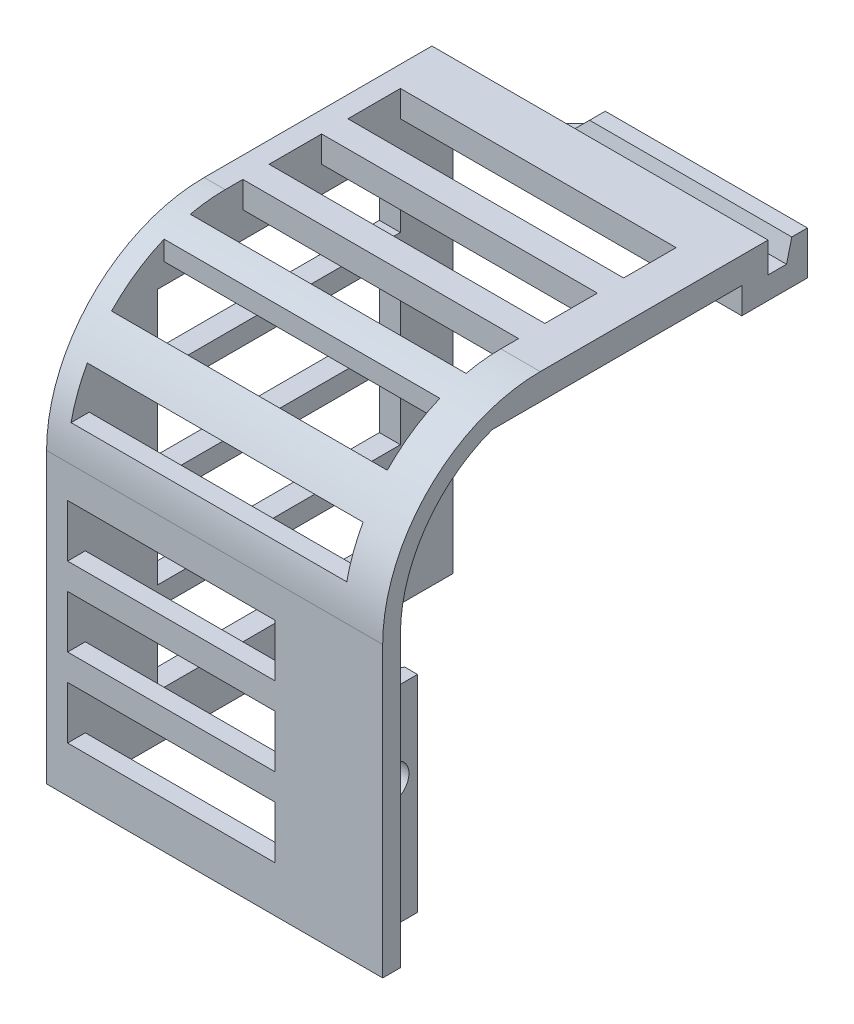
SolidWorks part; units mm, degrees
material "Nylon 6/10"
ref_plane "Front Plane" through (0, 0, 0) normal (0, 0, 1) x (1, 0, 0)
ref_plane "Top Plane" through (0, 0, 0) normal (0, 1, 0) x (1, 0, 0)
ref_plane "Right Plane" through (0, 0, 0) normal (1, 0, 0) x (0, 0, -1)
sketch "Sketch1" plane through (0, 0, 0) normal (1, 0, 0) x (0, 0, -1)
  line L0 (-2, 32) -> (-2, 30)
  line L2 (-2, 30) -> (0, 30)
  line L10 (1.408, 3) -> (0, 3) construction
  line L28 (-17.35, 34) -> (0, 34)
  line L29 (-28, 22) -> (-28, 15.7)
  line L30 (-23.7, 15.7) -> (-28, 15.7)
  line L31 (-28, 0) -> (-28, 15.7) construction
  line L33 (0, 34) -> (0, 32) construction
  line L34 (0, 34) -> (0, 30)
  line L37 (-2, 32) -> (-21.0137, 32)
  line L42 (-23.3, 15.7) -> (-16.7, 15.7) construction
  line L44 (1.408, 3) -> (0, 3) construction
  line L51 (-23.7, 15.7) -> (-23.7, 0)
  line L52 (-23.3, 3.3) -> (-23.3, 15.7) construction
  line L53 (-29.35, 0) -> (0, 0) construction
  line L54 (-28, 0) -> (0, 0) construction
  line L57 (-29.35, 0) -> (-23.7, 0)
  line L59 (-29.35, 22) -> (-29.35, 0) construction
  line L60 (-2.65, 15.701) -> (-20.95, 15.701) construction
  line L61 (-29.35, 22) -> (-29.35, 0)
  line L62 (-0.2, 3.8) -> (-0.2, 15.2) construction
  line L64 (-2.65, 15.701) -> (-20.95, 15.701) construction
  line L65 (-21.4252, 3.3) -> (-2.1748, 3.3) construction
  line L66 (-21.4252, 3.3) -> (-2.1748, 3.3) construction
  line L67 (-23.4, 15.2) -> (-23.4, 3.8) construction
  line L68 (-23.4, 15.2) -> (-23.4, 3.8) construction
  line L69 (-0.2, 3.8) -> (-0.2, 15.2) construction
  line L70 (4.4, 3.7) -> (4.4, 9.05) construction
  line L71 (4.4, 3.7) -> (4.4, 9.05) construction
  arc A0 (-21.0137, 32) -> (-28, 22) centre (-17.35, 22) ccw
  arc A2 (-17.35, 34) -> (-29.35, 22) centre (-17.35, 22) ccw construction
  circle A4 centre (-25.65, 9.5) radius 1.3 construction
  circle A5 centre (-25.65, 9.5) radius 1.3 construction
  arc A6 (3.1624, 9.95) -> (3.1624, 9.05) centre (2.05, 9.5) ccw construction
  arc A7 (3.1624, 9.95) -> (3.1624, 9.05) centre (2.05, 9.5) ccw construction
  arc A8 (-17.35, 34) -> (-29.35, 22) centre (-17.35, 22) ccw
  dimension "D1" = 2
  dimension "D2" = 2
  dimension "D3" = 1.35
  dimension "D4" = 0.4
  dimension "D5" = 2
extrude "Boss-Extrude1" add sketch "Sketch1" against normal offset from surface (25.6 mm away) 0.4
sketch "Sketch2" plane through (0, 0, 0) normal (1, 0, 0) x (0, 0, -1)
  line L0 (-23.7, 15.7) -> (-28, 15.7) construction
  line L1 (-23.7, 15.7) -> (-28, 15.7)
  line L2 (-23.7, 0) -> (-23.7, 15.7) construction
  line L3 (-23.7, 0) -> (-23.7, 15.7)
  line L6 (-28, 15.7) -> (-28, 0)
  line L7 (-23.7, 0) -> (-28, 0)
  line L8 (-29.35, 0) -> (-23.7, 0) construction
extrude "Cut-Extrude1" cut sketch "Sketch2" against normal blind 3
sketch "Sketch3" plane through (-3, 0, 0) normal (1, 0, 0) x (0, 0, -1)
  circle A0 centre (-25.65, 9.5) radius 1.3 construction
  circle A1 centre (-25.65, 9.5) radius 1.3
extrude "Cut-Extrude2" cut sketch "Sketch3" against normal up to next
sketch "Sketch4" plane through (-25.6, 0, 0) normal (-1, 0, 0) x (0, 0, 1)
  line L8 (0, 34) -> (0, 30)
  line L9 (0, 34) -> (0, 0)
  line L10 (17.35, 34) -> (0, 34)
  line L13 (0, 30) -> (2, 30)
  line L14 (2, 32) -> (21.0137, 32)
  line L15 (28, 22) -> (28, 15.7)
  line L16 (28, 15.7) -> (23.7, 15.7)
  line L17 (23.7, 15.7) -> (23.7, 0)
  line L18 (23.7, 0) -> (29.35, 0)
  line L19 (29.35, 0) -> (29.35, 22)
  line L20 (17.35, 34) -> (0, 34)
  line L28 (0, 0) -> (29.35, 0)
  line L29 (29.35, 0) -> (29.35, 22)
  line L31 (2, 30) -> (2, 32)
  arc A2 (29.35, 22) -> (17.35, 34) centre (17.35, 22) ccw
  arc A3 (28, 22) -> (21.0137, 32) centre (17.35, 22) ccw
  arc A4 (29.35, 22) -> (17.35, 34) centre (17.35, 22) ccw
  point P0 (4.8173, 0)
  dimension "D1" = 0
extrude "Boss-Extrude2" add sketch "Sketch4" against normal blind 1.6
sketch "Sketch6" plane through (0, 0, 0) normal (0, 0, -1) x (-1, 0, 0)
  line L0 (0, 32) -> (23, 32) construction
  line L1 (0, 32) -> (23, 32) construction
  line L2 (0, 31.7) -> (20, 31.7)
  line L3 (0, 30) -> (0, 34) construction
  line L4 (20, 31.7) -> (20, 30)
  line L5 (24, 30) -> (0, 30) construction
  line L6 (20, 30) -> (0, 30)
  line L7 (0, 30) -> (0, 31.7)
  point P6 (0, 0)
  dimension "D1" = 0.3
  dimension "D2" = 3
extrude "Boss-Extrude3" add sketch "Sketch6" along normal blind 3
chamfer "Chamfer2" distance 3 angle 45 1 edges at (-20, 30.85, -3)
sketch "Sketch8" plane through (0, 0, 0) normal (-1, 0, 0) x (0, 0, 1)
  line L0 (-1.408, 32) -> (-1.408, 34) construction
  line L1 (-1.408, 32) -> (-1.408, 34) construction
  line L2 (-1.408, 31.7) -> (-1.808, 33.3)
  line L3 (-3, 31.7) -> (0, 31.7) construction
  line L4 (-1.808, 33.3) -> (-3, 33.3)
  line L5 (-3, 33.3) -> (-3, 31.7)
  line L6 (-3, 31.7) -> (-1.408, 31.7)
  point P6 (-1.408, 31.7)
  point P8 (0, 0)
  point P9 (0, 0)
  point P10 (0, 0)
  point P11 (-1.5848, 32)
  point P12 (0, 0)
  point P14 (0, 0)
  point P15 (0, 0)
  dimension "D1" = 0.4
  dimension "D2" = 1.6
extrude "Boss-Extrude5" add sketch "Sketch8" along normal up to vertex (17 mm away) up to point (-17, 31.7, -3)
chamfer "Chamfer3" distance 1.6 angle 45 1 edges at (-17, 33.3, -2.404)
sketch "Sketch9" plane through (-24, 0, 0) normal (1, 0, 0) x (0, 0, -1)
  line L0 (-22.5137, 24.5) -> (-4, 24.5)
  line L1 (-4, 24.5) -> (-4, 30)
  line L2 (-4, 30) -> (-22.5137, 30)
  line L3 (-22.5137, 30) -> (-22.5137, 24.5)
  line L8 (-4, 30) -> (-4, 32) construction
  line L10 (0, 30) -> (0, 0) construction
  line L11 (-21.0137, 32) -> (-2, 32) construction
  dimension "D1" = 1.5
  dimension "D2" = 2
  dimension "D3" = 4
  dimension "D4" = 5.5
extrude "Cut-Extrude3" cut sketch "Sketch9" against normal up to next
pattern_linear "LPattern1" count 4 spacing 7 along (0, -1, 0) of "Cut-Extrude3"
sketch "Sketch10" plane through (0, 34, 0) normal (0, 1, 0) x (1, 0, 0)
  line L0 (-24, -8) -> (-3, -8)
  line L1 (-3, -8) -> (-3, -4)
  line L2 (-3, -4) -> (-24, -4)
  line L3 (-24, -4) -> (-24, -8)
  line L4 (-25.6, -4) -> (-24, -4) construction
  line L5 (-24, 0) -> (-24, -23.7) construction
  line L6 (0, -21.0137) -> (0, -2) construction
  dimension "D1" = 4
  dimension "D2" = 0
  dimension "D3" = 3
extrude "Cut-Extrude4" cut sketch "Sketch10" against normal up to next
pattern_linear "LPattern2" count 4 spacing 6 along (0, 0, 1) of "Cut-Extrude4"
sketch "Sketch11" plane through (-24, 0, 0) normal (1, 0, 0) x (0, 0, -1)
  line L4 (-23.7, 0) -> (-23.7, 15.7)
  line L5 (-23.7, 15.7) -> (-28, 15.7)
  line L6 (-28, 15.7) -> (-28, 0)
  line L7 (-28, 0) -> (-23.7, 0)
  line L8 (-23.7, 0) -> (-23.7, 15.7)
  line L9 (-23.7, 15.7) -> (-28, 15.7)
  line L11 (-28, 0) -> (-23.7, 0)
  line L12 (-28, 15.7) -> (-28, 0)
  dimension "D1" = 0
extrude "Cut-Extrude5" cut sketch "Sketch11" along normal offset from surface (20 mm away) 1 up to face at (-3, 9.5, 24.35)
chamfer "Chamfer4" distance 4.2 angle 45 1 edges at (-4, 7.85, 28)
sketch "Sketch12" plane through (0, 0, 28) normal (0, 0, -1) x (-1, 0, 0)
  line L0 (8.2, 3.5) -> (24, 3.5)
  line L1 (8.2, 15.7) -> (8.2, 0) construction
  line L2 (24, 0) -> (24, 22) construction
  line L3 (24, 3.5) -> (24, 7.5)
  line L4 (24, 7.5) -> (8.2, 7.5)
  line L5 (8.2, 7.5) -> (8.2, 3.5)
  line L7 (25.6, 3.5) -> (24, 3.5) construction
  dimension "D1" = 4
extrude "Cut-Extrude6" cut sketch "Sketch12" against normal up to next
pattern_linear "LPattern3" count 3 spacing 6 along (0, 1, 0) of "Cut-Extrude6"
sketch "Sketch13" plane through (0, 0, 29.35) normal (0, 0, 1) x (1, 0, 0)
  line L0 (-24, 24.5) -> (-3, 24.5)
  line L1 (-3, 24.5) -> (-3, 27.8173)
  line L2 (-3, 27.8173) -> (-24, 27.8173)
  line L3 (-24, 27.8173) -> (-24, 24.5)
  line L4 (-24, 30.3173) -> (-24, 33.0624) construction
  line L5 (-3, 33.0624) -> (-3, 30.3173) construction
  line L6 (-3, 30.3173) -> (-24, 30.3173) construction
  line L7 (-25.6, 22) -> (0, 22) construction
  dimension "D1" = 2.5
  dimension "D2" = 2.5
extrude "Cut-Extrude7" cut sketch "Sketch13" against normal up to next
